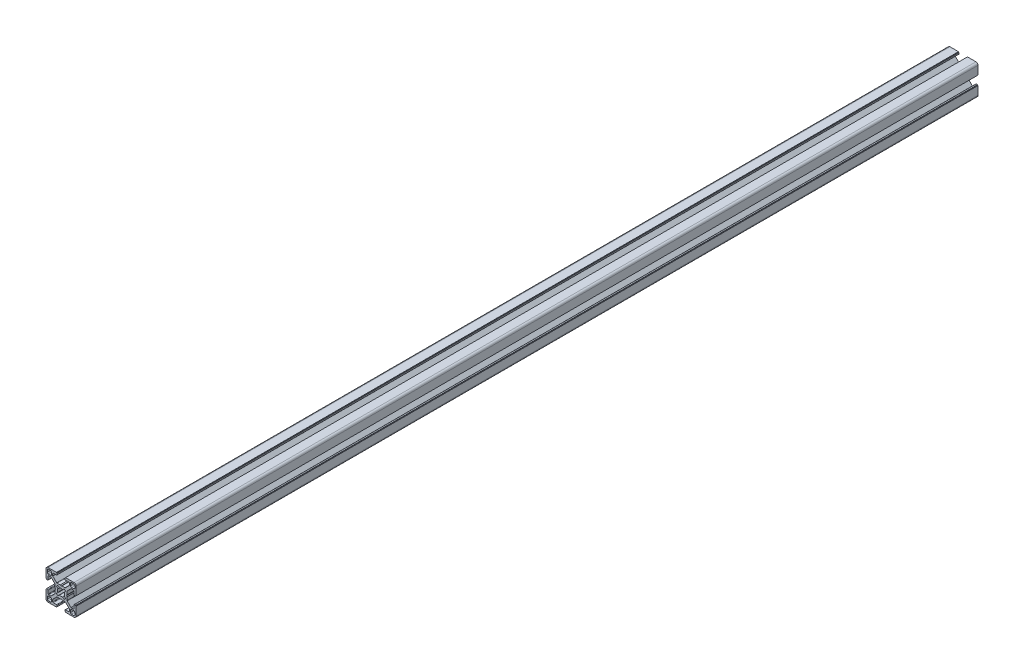
SolidWorks part; units mm, degrees
ref_plane "Front Plane" through (0, 0, 0) normal (0, 0, 1) x (1, 0, 0)
ref_plane "Top Plane" through (0, 0, 0) normal (0, 1, 0) x (1, 0, 0)
ref_plane "Right Plane" through (0, 0, 0) normal (1, 0, 0) x (0, 0, -1)
sketch "Sketch1" plane through (0, 0, 0) normal (0, 0, 1) x (1, 0, 0)
  line L0 (-15, 0) -> (15, 0) construction
  line L1 (0, -15) -> (0, 15) construction
  line L2 (-4.5, 15) -> (4.5, 15) construction
  line L3 (-4, -15) -> (4, -15) construction
  line L4 (-4.5, 15) -> (-4.5, 14.5)
  line L5 (-4.5, 14.5) -> (-4, 14.5)
  line L6 (-4, 14.5) -> (-4, 13.29)
  line L7 (-4.5, 12.79) -> (-7.7675, 12.79)
  line L8 (-8.2675, 12.29) -> (-8.2675, 10.2707)
  line L9 (-8.1211, 9.9171) -> (-4.3504, 6.1464)
  line L10 (-3.9968, 6) -> (0, 6)
  line L11 (0, 0) -> (-15, 15) construction
  line L12 (-4.5, 15) -> (-12.968, 15)
  line L14 (-12.705, 9.5135) -> (-10.5135, 9.5135)
  line L15 (-13.705, 10.5135) -> (-13.705, 12.705)
  line L16 (-12.705, 13.705) -> (-10.5135, 13.705)
  line L17 (-9.5135, 10.5135) -> (-9.5135, 12.705)
  line L18 (-13.705, 9.5135) -> (-9.5135, 13.705) construction
  line L19 (-13.705, 13.705) -> (-9.5135, 9.5135) construction
  line L20 (-3.1568, 4.5038) -> (-1.5303, 3.1477) construction
  line L21 (-4.5038, 3.1568) -> (-3.1477, 1.5303) construction
  line L22 (-6, 3.9968) -> (-6, 0)
  line L23 (-9.9171, 8.1211) -> (-6.1464, 4.3504)
  line L24 (-15, 4.5) -> (-15, 12.968)
  line L25 (-12.29, 8.2675) -> (-10.2707, 8.2675)
  line L26 (-12.79, 4.5) -> (-12.79, 7.7675)
  line L27 (-14.5, 4) -> (-13.29, 4)
  line L28 (-14.5, 4.5) -> (-14.5, 4)
  line L29 (-15, 4.5) -> (-14.5, 4.5)
  circle A0 centre (0, 0) radius 3.5
  arc A1 (-12.968, 15) -> (-15, 12.968) centre (-12.968, 12.968) ccw
  circle A2 centre (0, 0) radius 5.5 construction
  arc A3 (-10.5135, 9.5135) -> (-9.5135, 10.5135) centre (-10.5135, 10.5135) ccw
  arc A4 (-13.705, 12.705) -> (-12.705, 13.705) centre (-12.705, 12.705) cw
  arc A5 (-10.5135, 13.705) -> (-9.5135, 12.705) centre (-10.5135, 12.705) cw
  arc A6 (-12.705, 9.5135) -> (-13.705, 10.5135) centre (-12.705, 10.5135) cw
  arc A7 (-12.79, 4.5) -> (-13.29, 4) centre (-13.29, 4.5) cw
  arc A8 (-12.29, 8.2675) -> (-12.79, 7.7675) centre (-12.29, 7.7675) ccw
  arc A9 (-9.9171, 8.1211) -> (-10.2707, 8.2675) centre (-10.2707, 7.7675) ccw
  arc A10 (-6, 3.9968) -> (-6.1464, 4.3504) centre (-6.5, 3.9968) ccw
  arc A11 (-4.3504, 6.1464) -> (-3.9968, 6) centre (-3.9968, 6.5) ccw
  arc A12 (-4, 13.29) -> (-4.5, 12.79) centre (-4.5, 13.29) cw
  arc A13 (-7.7675, 12.79) -> (-8.2675, 12.29) centre (-7.7675, 12.29) ccw
  arc A14 (-8.2675, 10.2707) -> (-8.1211, 9.9171) centre (-7.7675, 10.2707) ccw
  point P4 (0, 0)
  point P8 (0, 0)
  point P13 (0, 15)
  point P15 (0, -15)
  point P16 (0, 6)
  point P23 (-11.6092, 11.6093)
  point P26 (0, 6)
  point P62 (-12.79, 4)
  point P65 (-12.79, 8.2675)
  point P68 (-10.0636, 8.2675)
  point P71 (-6, 4.2039)
  point P74 (-4.2039, 6)
  point P77 (-4, 12.79)
  point P80 (-8.2675, 12.79)
  point P83 (-8.2675, 10.0636)
  dimension "Center Hole Diameter" = 7
  dimension "D11" = 2.032
  dimension "D9" = 11
  dimension "D13" = 1
  dimension "D14" = 0.5
  dimension "Rail Height" = 30
  dimension "Rail Width" = 30
  dimension "T-Slot Width" = 8
  dimension "T-Slot Depth" = 9
  dimension "D1" = 9
  dimension "D2" = 45
  dimension "D3" = 8
  dimension "D4" = 2.21
  dimension "D5" = 16.535
  dimension "D7" = 2.54
  dimension "D6" = 1.295
  dimension "D8" = 1.246
  dimension "D10" = 10.36
  dimension "D12" = 1.905
sketch "Sketch2" plane through (0, 0, 0) normal (1, 0, 0) x (0, 0, -1)
  line L0 (-76.2, 0) -> (76.2, 0) construction
  line L2 (0, -15) -> (0, 15) construction
  line L3 (0, -15) -> (0, 15) construction
  line L4 (-76.2, -15) -> (-76.2, 15) construction
  line L5 (76.2, -15) -> (76.2, 15) construction
  point P0 (-38.7, 0)
  point P3 (0, 0)
  point P4 (38.7, 0)
  point P12 (-76.2, 0)
  point P14 (76.2, 0)
  dimension "Length" = 152.4
  dimension "D1" = 37.5
sketch "Sketch3" plane through (0, 0, 0) normal (0, 0, 1) x (1, 0, 0)
  line L0 (-4.5038, 3.1568) -> (-3.1477, 1.5303)
  line L1 (0, 3.5) -> (0, 5.5)
  line L2 (-5.5, 0) -> (-3.5, 0)
  line L7 (-6, 3.9968) -> (-6, 0) construction
  line L31 (-9.9171, 8.1211) -> (-6.1464, 4.3504) construction
  line L117 (-12.29, 8.2675) -> (-10.2707, 8.2675) construction
  line L118 (-12.79, 4.5) -> (-12.79, 7.7675) construction
  line L157 (-12.705, 9.5135) -> (-10.5135, 9.5135)
  line L158 (-9.5135, 10.5135) -> (-9.5135, 12.705)
  line L163 (-10.5135, 13.705) -> (-12.705, 13.705)
  line L164 (-13.705, 12.705) -> (-13.705, 10.5135)
  line L165 (-12.705, 9.5135) -> (-10.5135, 9.5135)
  line L166 (-9.5135, 10.5135) -> (-9.5135, 12.705)
  line L167 (-10.5135, 13.705) -> (-12.705, 13.705)
  line L168 (-13.705, 12.705) -> (-13.705, 10.5135)
  line L169 (-14.5, 4) -> (-13.29, 4) construction
  line L170 (-14.5, 4.5) -> (-14.5, 4) construction
  line L171 (-15, 4.5) -> (-14.5, 4.5) construction
  line L172 (-15, 4.5) -> (-15, 12.968) construction
  line L173 (-4.5, 15) -> (-12.968, 15) construction
  line L174 (-4.5, 15) -> (-4.5, 14.5) construction
  line L175 (-4.5, 14.5) -> (-4, 14.5) construction
  line L176 (-4, 14.5) -> (-4, 13.29) construction
  line L177 (-4.5, 12.79) -> (-7.7675, 12.79) construction
  line L178 (-8.2675, 12.29) -> (-8.2675, 10.2707) construction
  line L179 (-8.1211, 9.9171) -> (-4.3504, 6.1464) construction
  line L180 (-3.9968, 6) -> (0, 6) construction
  line L181 (-6, 3.9968) -> (-6, 0.866)
  line L182 (-9.9171, 8.1211) -> (-6.1464, 4.3504)
  line L183 (-12.29, 8.2675) -> (-10.2707, 8.2675)
  line L184 (-12.79, 4.5) -> (-12.79, 7.7675)
  line L185 (-14.5, 4) -> (-13.29, 4)
  line L186 (-14.5, 4.5) -> (-14.5, 4)
  line L187 (-15, 4.5) -> (-14.5, 4.5)
  line L188 (-15, 4.5) -> (-15, 12.968)
  line L189 (-4.5, 15) -> (-12.968, 15)
  line L190 (-4.5, 15) -> (-4.5, 14.5)
  line L191 (-4.5, 14.5) -> (-4, 14.5)
  line L192 (-4, 14.5) -> (-4, 13.29)
  line L193 (-4.5, 12.79) -> (-7.7675, 12.79)
  line L194 (-8.2675, 12.29) -> (-8.2675, 10.2707)
  line L195 (-8.1211, 9.9171) -> (-4.3504, 6.1464)
  line L196 (-3.9968, 6) -> (-0.866, 6)
  line L197 (-0.866, 6) -> (0, 5.5)
  line L198 (0, -15) -> (0, 15) construction
  line L199 (0, 0) -> (-15, 15) construction
  line L200 (0, 0) -> (-15, 15) construction
  line L201 (-3.1568, 4.5038) -> (-1.5303, 3.1477) construction
  line L202 (-3.1568, 4.5038) -> (-1.5303, 3.1477)
  line L203 (-6, 0.866) -> (-5.5, 0)
  line L204 (-15, 0) -> (15, 0) construction
  line L205 (-15, 0) -> (15, 0) construction
  line L206 (0, -15) -> (0, 15) construction
  arc A0 (-3.5, 0) -> (-3.1477, 1.5303) centre (0, 0) cw
  arc A10 (-6, 3.9968) -> (-6.1464, 4.3504) centre (-6.5, 3.9968) ccw construction
  circle A16 centre (0, 0) radius 3.5
  arc A18 (0, 3.5) -> (-1.5303, 3.1477) centre (0, 0) ccw
  arc A20 (-9.9171, 8.1211) -> (-10.2707, 8.2675) centre (-10.2707, 7.7675) ccw construction
  arc A22 (-12.29, 8.2675) -> (-12.79, 7.7675) centre (-12.29, 7.7675) ccw construction
  arc A28 (-13.29, 4) -> (-12.79, 4.5) centre (-13.29, 4.5) ccw construction
  arc A29 (-10.5135, 9.5135) -> (-9.5135, 10.5135) centre (-10.5135, 10.5135) ccw
  arc A30 (-9.5135, 12.705) -> (-10.5135, 13.705) centre (-10.5135, 12.705) ccw
  arc A31 (-12.705, 13.705) -> (-13.705, 12.705) centre (-12.705, 12.705) ccw
  arc A32 (-13.705, 10.5135) -> (-12.705, 9.5135) centre (-12.705, 10.5135) ccw
  arc A33 (-10.5135, 9.5135) -> (-9.5135, 10.5135) centre (-10.5135, 10.5135) ccw
  arc A34 (-9.5135, 12.705) -> (-10.5135, 13.705) centre (-10.5135, 12.705) ccw
  arc A35 (-12.705, 13.705) -> (-13.705, 12.705) centre (-12.705, 12.705) ccw
  arc A36 (-13.705, 10.5135) -> (-12.705, 9.5135) centre (-12.705, 10.5135) ccw
  arc A37 (-12.968, 15) -> (-15, 12.968) centre (-12.968, 12.968) ccw construction
  arc A38 (-4.5, 12.79) -> (-4, 13.29) centre (-4.5, 13.29) ccw construction
  arc A39 (-7.7675, 12.79) -> (-8.2675, 12.29) centre (-7.7675, 12.29) ccw construction
  arc A40 (-8.2675, 10.2707) -> (-8.1211, 9.9171) centre (-7.7675, 10.2707) ccw construction
  arc A41 (-4.3504, 6.1464) -> (-3.9968, 6) centre (-3.9968, 6.5) ccw construction
  arc A42 (-6, 3.9968) -> (-6.1464, 4.3504) centre (-6.5, 3.9968) ccw
  arc A43 (-9.9171, 8.1211) -> (-10.2707, 8.2675) centre (-10.2707, 7.7675) ccw
  arc A44 (-12.29, 8.2675) -> (-12.79, 7.7675) centre (-12.29, 7.7675) ccw
  arc A45 (-13.29, 4) -> (-12.79, 4.5) centre (-13.29, 4.5) ccw
  arc A46 (-12.968, 15) -> (-15, 12.968) centre (-12.968, 12.968) ccw
  arc A47 (-4.5, 12.79) -> (-4, 13.29) centre (-4.5, 13.29) ccw
  arc A48 (-7.7675, 12.79) -> (-8.2675, 12.29) centre (-7.7675, 12.29) ccw
  arc A49 (-8.2675, 10.2707) -> (-8.1211, 9.9171) centre (-7.7675, 10.2707) ccw
  arc A50 (-4.3504, 6.1464) -> (-3.9968, 6) centre (-3.9968, 6.5) ccw
  circle A51 centre (0, 0) radius 5.5 construction
  arc A52 (-3.1568, 4.5038) -> (-4.5038, 3.1568) centre (0, 0) ccw
  dimension "D3" = 60
  dimension "D4" = 60
  dimension "D1" = 0
  dimension "D2" = 0
extrude "Boss-Extrude1" add sketch "Sketch3" along normal mid plane 900
pattern_circular "CirPattern1" count 4 over 360 about axis through (0, 0, 76.2) along (0, 0, -1) of "Boss-Extrude1"
ref_plane "Contact Plane1" through (15, 0, 0) normal (1, 0, 0) x (0, 0, -1)
ref_plane "Contact Plane2" through (0, -15, 0) normal (0, 1, 0) x (1, 0, 0)
ref_plane "Contact Plane3" through (-15, 0, 0) normal (1, 0, 0) x (0, 0, -1)
ref_plane "Contact Plane4" through (0, 15, 0) normal (0, 1, 0) x (1, 0, 0)
equation "\"D1@Sketch2\" = \"Rail Height@Sketch1\" * 1.25"
equation "\"D1@Sketch1\"=\"T-Slot Width@Sketch1\"+1mm"
equation "\"D3@Sketch1\"=\"T-Slot Width@Sketch1\""
equation "\"D1@Boss-Extrude1\"=\"length\""
equation "\"length\" = 900"
